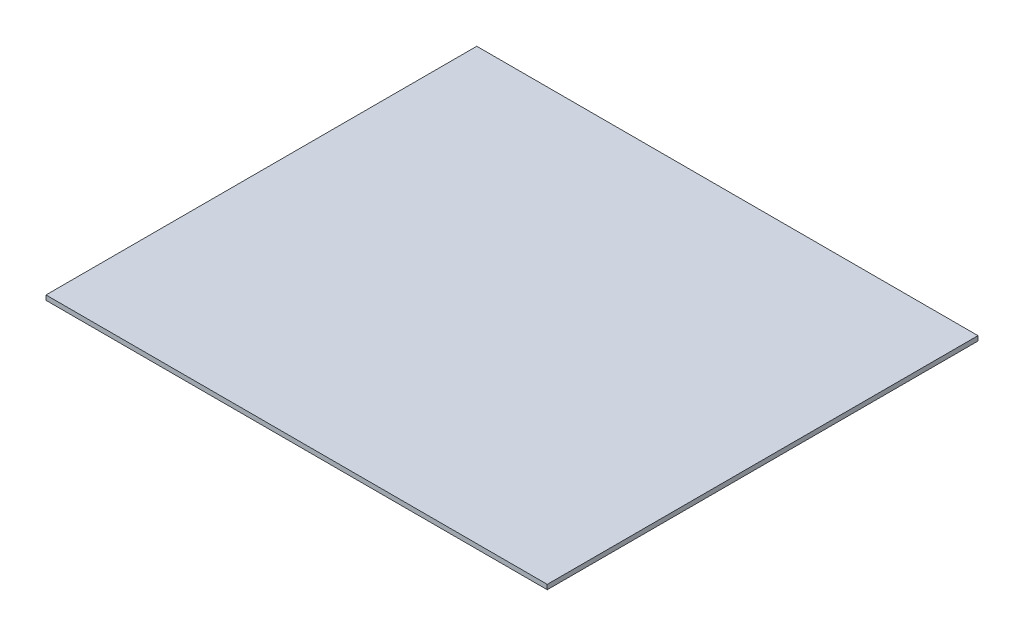
SolidWorks part; units mm, degrees
material "Acrílico (Impacto medio-alto)"
ref_plane "Alzado" through (0, 0, 0) normal (0, 0, 1) x (1, 0, 0)
ref_plane "Planta" through (0, 0, 0) normal (0, 1, 0) x (1, 0, 0)
ref_plane "Vista lateral" through (0, 0, 0) normal (1, 0, 0) x (0, 0, -1)
sketch "Sketch1" plane through (0, 0, 0) normal (0, 1, 0) x (1, 0, 0)
  line L1 (-160, -137.5) -> (160, -137.5)
  line L2 (-160, -137.5) -> (-160, 137.5)
  line L3 (-160, 137.5) -> (160, 137.5)
  line L4 (160, -137.5) -> (160, 137.5)
  line L5 (-160, -137.5) -> (160, 137.5) construction
  line L6 (-160, 137.5) -> (160, -137.5) construction
  point P0 (0, 0)
  dimension "D1" = 320
  dimension "D2" = 275
extrude "Boss-Extrude1" add sketch "Sketch1" along normal blind 3
